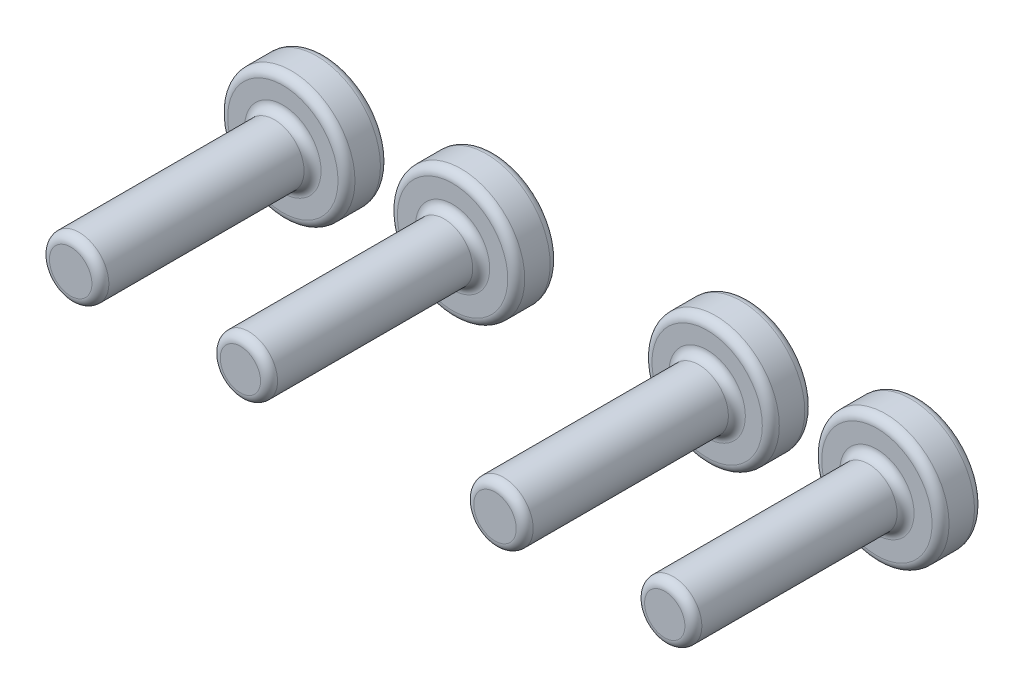
SolidWorks part; units mm, degrees
ref_plane "Ebene vorne" through (0, 0, 0) normal (0, 0, 1) x (1, 0, 0)
ref_plane "Ebene oben" through (0, 0, 0) normal (0, 1, 0) x (1, 0, 0)
ref_plane "Ebene rechts" through (0, 0, 0) normal (1, 0, 0) x (0, 0, -1)
sketch "Sketch1" plane through (0, 0, 0) normal (0, 0, 1) x (1, 0, 0)
  circle A0 centre (-8.723, 2.9152) radius 0.7
  circle A1 centre (-4.723, 2.9152) radius 0.675
  circle A2 centre (5.277, 2.9152) radius 0.675
  circle A3 centre (1.277, 2.9152) radius 0.7
  dimension "D1" = 1.4
  dimension "D2" = 1.35
  dimension "D4" = 4
  dimension "D3" = 2
extrude "Boss-Extrude1" add sketch "Sketch1" along normal blind 5
sketch "Sketch2" plane through (0, 0, 0) normal (0, 0, 1) x (1, 0, 0)
  circle A0 centre (-8.723, 2.9152) radius 1.5
  circle A1 centre (-4.723, 2.9152) radius 1.5
  circle A2 centre (5.277, 2.9152) radius 1.5
  circle A3 centre (1.277, 2.9152) radius 1.5
  dimension "D2" = 3
  dimension "D3" = 3
  dimension "D1" = 2
extrude "Boss-Extrude2" add sketch "Sketch2" against normal blind 1
fillet "Fillet1" radius 0.2 4 edges at (-7.223, 2.9152, 0) (-7.223, 2.9152, -1) (-8.023, 2.9152, 0) (-8.023, 2.9152, 5)
fillet "Fillet2" radius 0.2 4 edges at (-3.223, 2.9152, -1) (-4.048, 2.9152, 0) (-4.048, 2.9152, 5) (-3.223, 2.9152, 0)
fillet "Fillet3" radius 0.2 4 edges at (2.777, 2.9152, 0) (2.777, 2.9152, -1) (1.977, 2.9152, 0) (1.977, 2.9152, 5)
fillet "Fillet4" radius 0.2 4 edges at (5.952, 2.9152, 0) (5.952, 2.9152, 5) (6.777, 2.9152, 0) (6.777, 2.9152, -1)
sketch "Sketch3" plane through (0, 0, 0) normal (0, 0, 1) x (1, 0, 0)
  text T0 "1.4       1.35             1.35       1.4" font "Century Gothic" height 0.8
extrude "Cut-Extrude1" cut sketch "Sketch3" against normal blind 1 from offset 0.5 offset against normal yes
